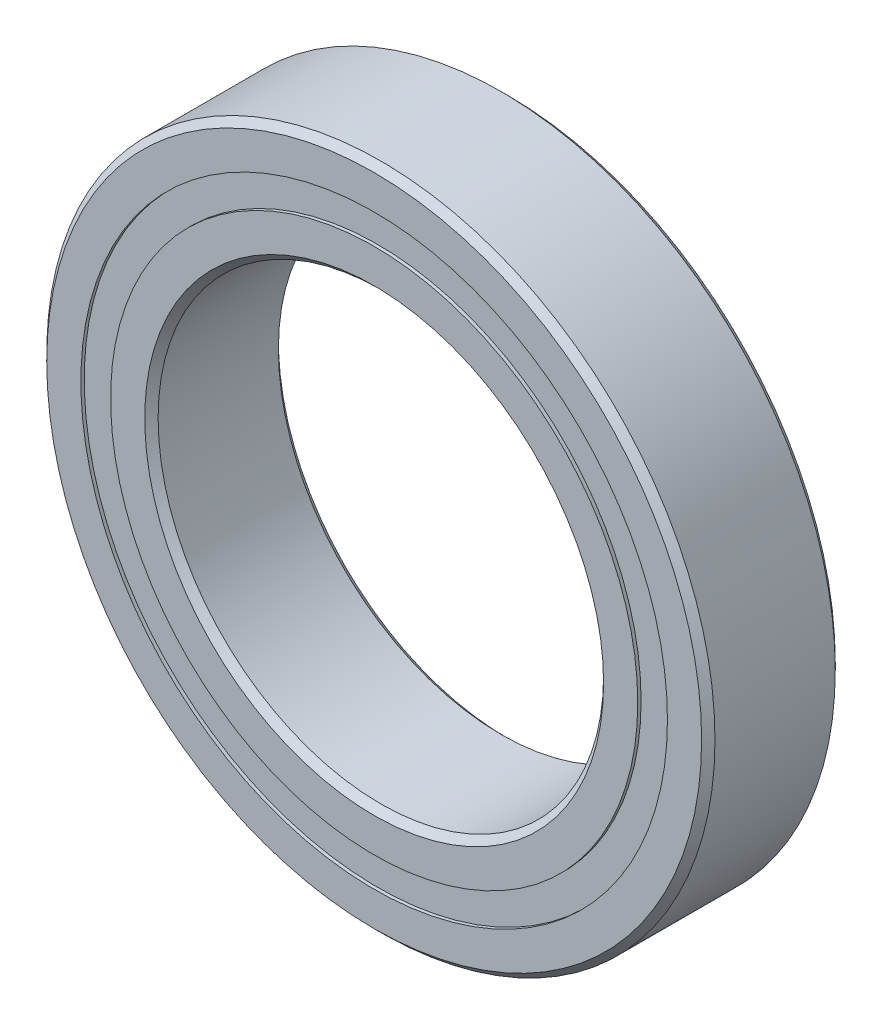
SolidWorks part; units mm, degrees
ref_plane "Front Plane" through (0, 0, 0) normal (0, 0, 1) x (1, 0, 0)
ref_plane "Top Plane" through (0, 0, 0) normal (0, 1, 0) x (1, 0, 0)
ref_plane "Right Plane" through (0, 0, 0) normal (1, 0, 0) x (0, 0, -1)
sketch "Sketch1" plane through (0, 0, 0) normal (1, 0, 0) x (0, 0, -1)
  line L0 (-1.5, 0) -> (1.5, 0) construction
  line L1 (0, 7.5) -> (0, -7.5) construction
  line L2 (1.35, 7.5) -> (-1.35, 7.5)
  line L3 (-1.35, 7.5) -> (-1.5, 7.35)
  line L4 (-1.5, 7.35) -> (-1.5, 6.5833)
  line L5 (-1.5, 6.5833) -> (-0.6667, 6.5833)
  line L6 (1.5, 6.5833) -> (0.6667, 6.5833)
  line L7 (1.5, 7.35) -> (1.5, 6.5833)
  line L8 (1.35, 7.5) -> (1.5, 7.35)
  line L9 (0, 7.5) -> (0, 6.25) construction
  line L10 (0, 6.25) -> (0, 5) construction
  arc A0 (-0.6667, 6.5833) -> (0.6667, 6.5833) centre (0, 6.25) cw
  arc A1 (-0.6667, 6.5833) -> (0.6667, 6.5833) centre (0, 6.25) ccw construction
  point P14 (0, 5)
  point P15 (0, -5)
  dimension "Width" = 3
  dimension "OD" = 15
  dimension "D1" = 45
  dimension "D2" = 0.15
  dimension "D3" = 1.3333
  dimension "Shaft Dia" = 10
  dimension "D4" = 0.3333
revolve "Revolve1" add sketch "Sketch1" angle 360 about L0
sketch "Sketch2" plane through (0, 0, 0) normal (1, 0, 0) x (0, 0, -1)
  line L0 (-1.5, 5.9167) -> (-0.6667, 5.9167)
  line L1 (-1.5, 7.35) -> (-1.5, -7.35) construction
  line L2 (-1.5, 5.9167) -> (-1.5, 5.15)
  line L3 (-1.5, 5.15) -> (-1.35, 5)
  line L4 (-1.35, 5) -> (1.35, 5)
  line L5 (0, 7.5) -> (0, -7.5) construction
  line L6 (0, 5) -> (0, 5.5046) construction
  line L7 (0, 5.5046) -> (0, 5) construction
  line L8 (-1.5, 5.9167) -> (-1.5, 4.3833) construction
  line L10 (1.5, 5.9167) -> (0.6667, 5.9167)
  line L11 (1.5, 5.9167) -> (1.5, 5.15)
  line L12 (1.5, 5.15) -> (1.35, 5)
  arc A0 (-0.6667, 5.9167) -> (0.6667, 5.9167) centre (0, 6.25) ccw
  arc A1 (0.6667, 6.5833) -> (-0.6667, 6.5833) centre (0, 6.25) ccw construction
  circle A2 centre (0, 6.25) radius 0.7454 construction
  dimension "D1" = 0.15
  dimension "D2" = 45
revolve "Revolve2" add sketch "Sketch2" angle 360 about L0
sketch "Sketch3" plane through (0, 0, 0) normal (1, 0, 0) x (0, 0, -1)
  line L0 (-0.7454, 6.25) -> (0.7454, 6.25)
  line L1 (0, 6.25) -> (0, 0) construction
  circle A1 centre (0, 6.25) radius 0.7454 construction
  arc A2 (-0.7454, 6.25) -> (0.7454, 6.25) centre (0, 6.25) cw
  arc A3 (0.6667, 6.5833) -> (-0.6667, 6.5833) centre (0, 6.25) ccw construction
  dimension "D1" = 1.4907
  dimension "D2" = 6.25
revolve "Revolve3" add sketch "Sketch3" angle 360 about L0
ref_axis "Axis1" through (0, 0, -1.5) along (0, 0, 1)
pattern_circular "CirPattern1" count 25 every 14.4 about axis through (0, 0, -1.5) along (0, 0, 1) of bodies 104
sketch "Sketch5" plane through (0, 0, 0) normal (1, 0, 0) x (0, 0, -1)
  line L0 (-1.5, 5.9167) -> (-0.6667, 5.9167) construction
  line L1 (-1.425, 6.5833) -> (-0.7454, 6.5833)
  line L2 (-1.425, 6.5833) -> (-1.425, 5.9167)
  line L3 (-1.425, 5.9167) -> (-0.7454, 5.9167)
  line L4 (-0.7454, 6.5833) -> (-0.7454, 5.9167)
  line L5 (0.7454, 6.5833) -> (1.425, 6.5833)
  line L6 (0.7454, 6.5833) -> (0.7454, 5.9167)
  line L7 (0.7454, 5.9167) -> (1.425, 5.9167)
  line L8 (1.425, 6.5833) -> (1.425, 5.9167)
  line L9 (-1.5, 6.5833) -> (-0.6667, 6.5833) construction
  line L10 (-1.425, 7.425) -> (-1.425, 6.5833) construction
  line L11 (-1.35, 7.5) -> (-1.5, 7.35) construction
  circle A0 centre (0, 6.25) radius 0.7454 construction
revolve "Revolve5" add sketch "Sketch5" angle 360 about L0
sketch "Sketch6" plane through (0, 0, 0) normal (0, 1, 0) x (1, 0, 0)
  point P0 (7.5, -1.5)
  point P1 (7.5, 1.5)
  dimension "D1" = 3
ref_axis "Center Axis 1" through (0, 0, -3.9661) along (0, 0, 1)
ref_plane "Contact Plane 1" through (0, 0, 1.5) normal (0, 0, 1) x (1, 0, 0)
ref_plane "Contact Plane 2" through (0, 0, -1.5) normal (0, 0, -1) x (-1, 0, 0)
equation "\"D2@Sketch1\" = \"Width@Sketch1\"*.05"
equation "\"D3@Sketch1\" = \"Width@Sketch1\"/2.25"
equation "\"D4@Sketch1\" = \"D3@Sketch1\"/4"
equation "\"Balls@CirPattern1\"=\"D2@Sketch3\"*2*pi/\"D1@Sketch3\"-1"
equation "\"D2@CirPattern1\" = 360/\"Balls@CirPattern1\""
equation "\"D1@Sketch2\"=\"D2@Sketch1\""
equation "\"D1@Sketch6\"=\"Width@Sketch1\""
